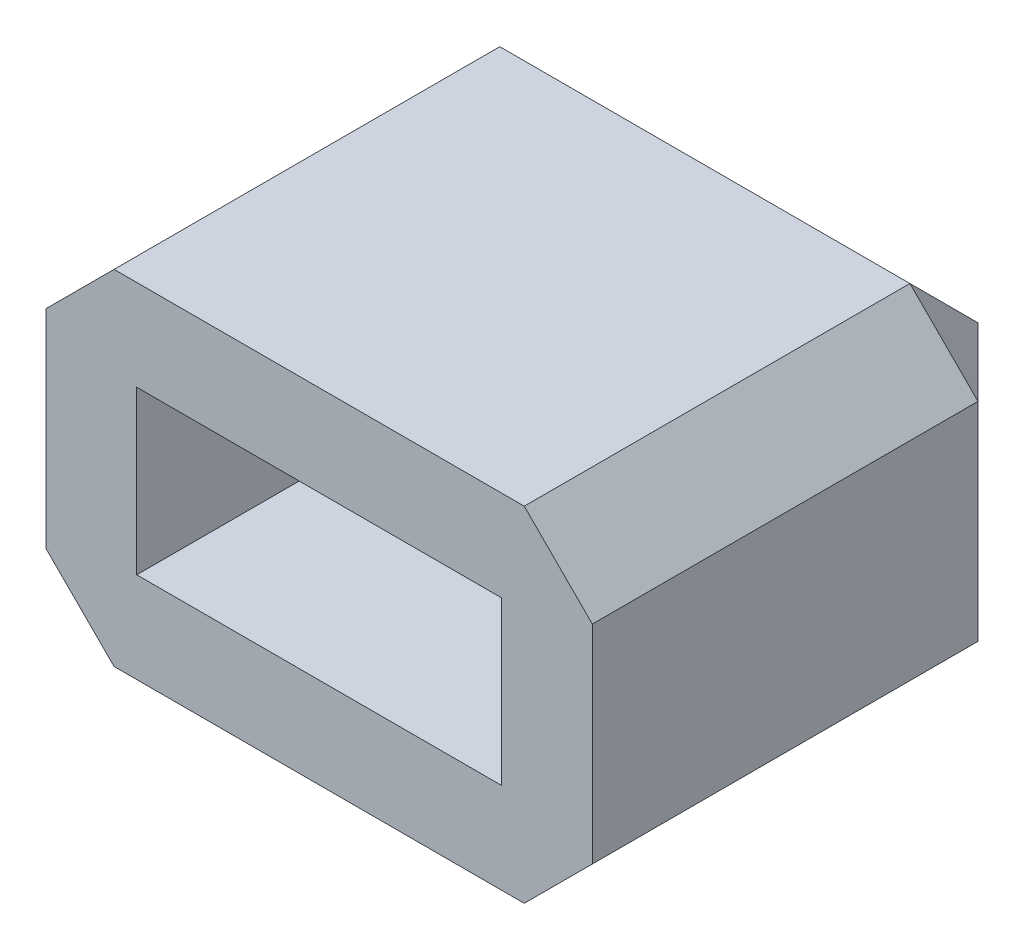
SolidWorks part; units mm, degrees
ref_plane "Front Plane" through (0, 0, 0) normal (0, 0, 1) x (1, 0, 0)
ref_plane "Top Plane" through (0, 0, 0) normal (0, 1, 0) x (1, 0, 0)
ref_plane "Right Plane" through (0, 0, 0) normal (1, 0, 0) x (0, 0, -1)
sketch "Sketch1" plane through (0, 0, 0) normal (0, 0, 1) x (1, 0, 0)
  line L1 (4.02, -1.79) -> (-4.02, -1.79)
  line L2 (4.02, -1.79) -> (4.02, 1.79)
  line L3 (4.02, 1.79) -> (-4.02, 1.79)
  line L4 (-4.02, -1.79) -> (-4.02, 1.79)
  line L5 (0, 1.79) -> (0, -1.79) construction
  line L6 (4.02, 0) -> (-4.02, 0) construction
  line L7 (-6.02, 3.79) -> (6.02, 3.79)
  line L8 (-6.02, 3.79) -> (-6.02, -3.79)
  line L9 (-6.02, -3.79) -> (6.02, -3.79)
  line L10 (6.02, 3.79) -> (6.02, -3.79)
  line L11 (0, -3.79) -> (0, 3.79) construction
  line L12 (-6.02, 0) -> (6.02, 0) construction
  point P0 (0, 0)
  point P4 (0, 0)
  dimension "D1" = 3.58
  dimension "D2" = 8.04
  dimension "D3" = 2
  dimension "D4" = 2
extrude "Boss-Extrude1" add sketch "Sketch1" along normal blind 8
extrude "Boss-Extrude2" add sketch "Sketch1<2>" against normal blind 2 contours L4 L1 L2 L3 | L10 L7 L8 L9 L1 L4 L3 L2 region at (0, 0, 0) region at (0, 3.6477, 0)
sketch "Sketch1<2>" plane through (0, 0, 0) normal (0, 0, 1) x (1, 0, 0) same geometry as "Sketch1"
chamfer "Chamfer1" distance 1.5 angle 45 8 edges at (-6.02, -3.79, 3) (0, -3.79, -2) (-6.02, 0, -2) (-6.02, 3.79, 3) (0, 3.79, -2) (6.02, 3.79, 3) (6.02, -3.79, 3) (6.02, 0, -2)
equation "\"LF\" = 0.04mm"
equation "\"TF\" = 0.02mm"
equation "\"AngLF\"= 0.5"
equation "\"AngTF\"= 0.3"
equation "\"D2@Sketch1\"=8+2*\"TF\""
equation "\"D1@Sketch1\"=3.5+2*\"LF\""
